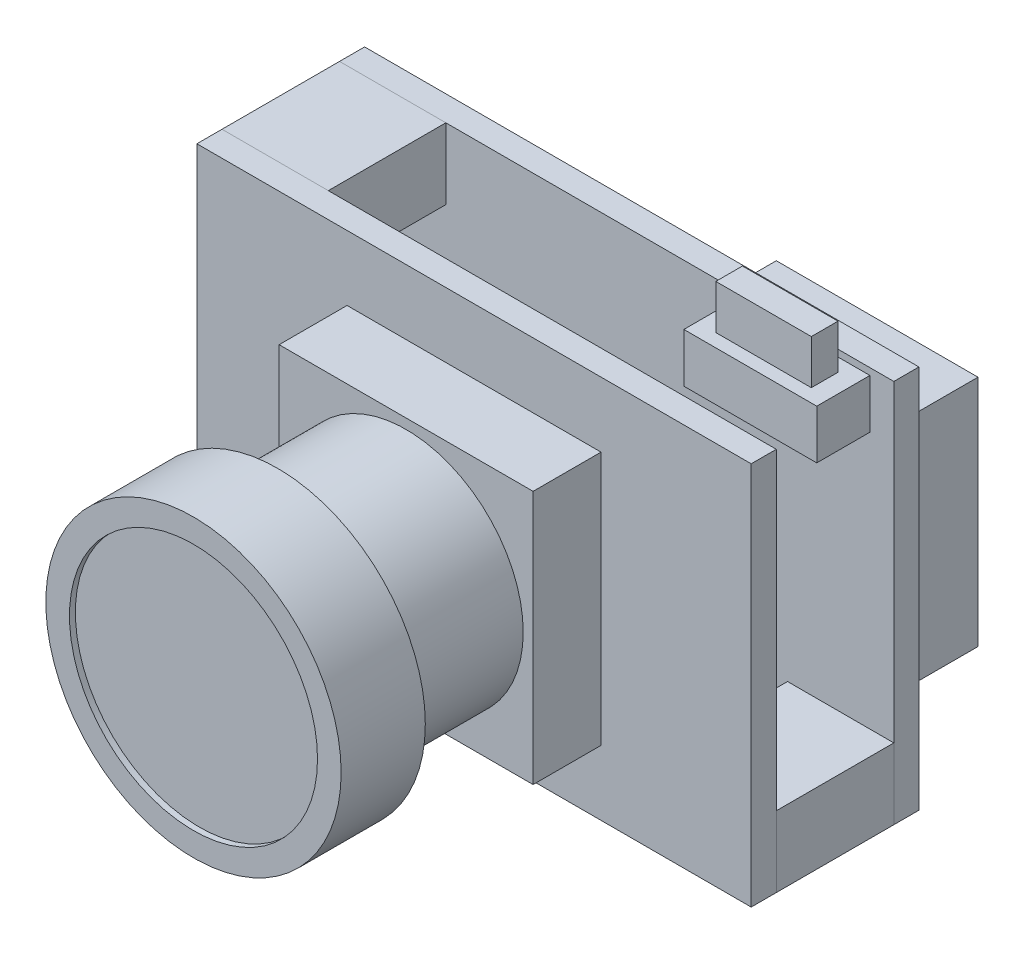
SolidWorks part; units mm, degrees
ref_plane "Front Plane" through (0, 0, 0) normal (0, 0, 1) x (1, 0, 0)
ref_plane "Top Plane" through (0, 0, 0) normal (0, 1, 0) x (1, 0, 0)
ref_plane "Right Plane" through (0, 0, 0) normal (1, 0, 0) x (0, 0, -1)
sketch "Sketch1" plane through (0, 0, 0) normal (0, 0, 1) x (1, 0, 0)
  line L1 (-9.385, 6.5) -> (9.385, 6.5)
  line L2 (-9.385, 6.5) -> (-9.385, -6.5)
  line L3 (-9.385, -6.5) -> (9.385, -6.5)
  line L4 (9.385, 6.5) -> (9.385, -6.5)
  line L5 (-9.385, 6.5) -> (9.385, -6.5) construction
  line L6 (-9.385, -6.5) -> (9.385, 6.5) construction
  point P0 (0, 0)
  dimension "D1" = 13
  dimension "D2" = 18.77
extrude "Boss-Extrude1" add sketch "Sketch1" along normal blind 0.85
sketch "Sketch2" plane through (0, 0, 0.85) normal (0, 0, 1) x (1, 0, 0)
  line L1 (9.385, -6.5) -> (5.785, -6.5)
  line L2 (9.385, -6.5) -> (9.385, -4.1)
  line L3 (9.385, -4.1) -> (5.785, -4.1)
  line L4 (5.785, -6.5) -> (5.785, -4.1)
  line L5 (-9.385, 6.5) -> (-5.785, 6.5)
  line L6 (-9.385, 6.5) -> (-9.385, 4.1)
  line L7 (-9.385, 4.1) -> (-5.785, 4.1)
  line L8 (-5.785, 6.5) -> (-5.785, 4.1)
  dimension "D1" = 2.4
  dimension "D2" = 3.6
extrude "Boss-Extrude2" add sketch "Sketch2" along normal blind 3.98 separate body
sketch "Sketch3" plane through (0, 0, 4.83) normal (0, 0, 1) x (1, 0, 0)
  line L0 (9.385, -6.5) -> (9.385, -4.1) construction
  line L1 (-9.385, 6.5) -> (9.385, 6.5)
  line L2 (-9.385, 6.5) -> (-9.385, -6.5)
  line L3 (-9.385, -6.5) -> (9.385, -6.5)
  line L4 (9.385, 6.5) -> (9.385, -6.5)
  line L5 (5.785, -6.5) -> (9.385, -6.5) construction
extrude "Boss-Extrude3" add sketch "Sketch3" along normal blind 0.85
sketch "Sketch4" plane through (0, 0, 5.68) normal (0, 0, 1) x (1, 0, 0)
  line L1 (-4.3, 4.3) -> (4.3, 4.3)
  line L2 (-4.3, 4.3) -> (-4.3, -4.3)
  line L3 (-4.3, -4.3) -> (4.3, -4.3)
  line L4 (4.3, 4.3) -> (4.3, -4.3)
  line L5 (-4.3, 4.3) -> (4.3, -4.3) construction
  line L6 (-4.3, -4.3) -> (4.3, 4.3) construction
  point P0 (0, 0)
  dimension "D1" = 8.6
extrude "Boss-Extrude4" add sketch "Sketch4" along normal blind 2.3
sketch "Sketch5" plane through (0, 0, 7.98) normal (0, 0, 1) x (1, 0, 0)
  circle A0 centre (0, 0) radius 3.965
  dimension "D1" = 7.93
extrude "Boss-Extrude5" add sketch "Sketch5" along normal blind 4.35
sketch "Sketch6" plane through (0, 0, 12.33) normal (0, 0, 1) x (1, 0, 0)
  circle A0 centre (0, 0) radius 5
  dimension "D1" = 10
extrude "Boss-Extrude6" add sketch "Sketch6" along normal blind 2.85
sketch "Sketch7" plane through (0, 0, 15.18) normal (0, 0, 1) x (1, 0, 0)
  circle A0 centre (0, 0) radius 4.2
  circle A1 centre (0, 0) radius 5 construction
  dimension "D1" = 0.8
extrude "Cut-Extrude1" cut sketch "Sketch7" against normal blind 0.2
sketch "Sketch8" plane through (0, 0, 0) normal (0, 0, -1) x (-1, 0, 0)
  line L0 (-9.385, -6.5) -> (-9.385, 6.5) construction
  line L1 (-9.085, 4.9) -> (-2.255, 4.9)
  line L2 (-9.085, 4.9) -> (-9.085, -3)
  line L3 (-9.085, -3) -> (-2.255, -3)
  line L4 (-2.255, 4.9) -> (-2.255, -3)
  line L5 (-9.385, 6.5) -> (9.385, 6.5) construction
  dimension "D1" = 7.9
  dimension "D2" = 6.83
  dimension "D3" = 0.3
  dimension "D4" = 1.6
extrude "Boss-Extrude7" add sketch "Sketch8" along normal blind 2.3
sketch "Sketch9" plane through (0, 0, 0) normal (0, 0, -1) x (-1, 0, 0)
  line L1 (-0.6481, -5.1764) -> (5.3519, -5.1764)
  line L2 (-0.6481, -5.1764) -> (-0.6481, 0.8236)
  line L3 (-0.6481, 0.8236) -> (5.3519, 0.8236)
  line L4 (5.3519, -5.1764) -> (5.3519, 0.8236)
  dimension "D1" = 6
extrude "Boss-Extrude8" add sketch "Sketch9" along normal blind 1
sketch "Sketch10" plane through (0, 0, 0.85) normal (0, 0, 1) x (1, 0, 0)
  line L1 (8.5749, 6.2701) -> (4.0749, 6.2701)
  line L2 (8.5749, 6.2701) -> (8.5749, 4.6059)
  line L3 (8.5749, 4.6059) -> (4.0749, 4.6059)
  line L4 (4.0749, 6.2701) -> (4.0749, 4.6059)
  dimension "D1" = 4.5
extrude "Boss-Extrude9" add sketch "Sketch10" along normal blind 1.8
sketch "Sketch11" plane through (0, 6.2701, 0) normal (0, 1, 0) x (1, 0, 0)
  line L0 (8.5749, -0.85) -> (4.0749, -2.65) construction
  line L1 (8.5749, -2.65) -> (4.0749, -2.65) construction
  line L2 (4.0749, -2.65) -> (4.0749, -0.85) construction
  line L4 (4.7074, -1.2989) -> (7.9423, -1.2989)
  line L5 (4.7074, -1.2989) -> (4.7074, -2.2011)
  line L6 (4.7074, -2.2011) -> (7.9423, -2.2011)
  line L7 (7.9423, -1.2989) -> (7.9423, -2.2011)
  line L8 (4.7074, -1.2989) -> (7.9423, -2.2011) construction
  line L9 (4.7074, -2.2011) -> (7.9423, -1.2989) construction
  point P7 (6.3249, -1.75)
extrude "Boss-Extrude10" add sketch "Sketch11" along normal blind 1.5
sketch "Sketch12" plane through (0, 0, 0.85) normal (0, 0, 1) x (1, 0, 0)
  line L1 (-3.6639, 1.1451) -> (-6.0818, 1.1451)
  line L2 (-3.6639, 1.1451) -> (-3.6639, -1.1451)
  line L3 (-3.6639, -1.1451) -> (-6.0818, -1.1451)
  line L4 (-6.0818, 1.1451) -> (-6.0818, -1.1451)
  line L5 (-3.6639, 1.1451) -> (-6.0818, -1.1451) construction
  line L6 (-3.6639, -1.1451) -> (-6.0818, 1.1451) construction
  point P0 (-4.8729, 0)
extrude "Boss-Extrude11" add sketch "Sketch12" along normal blind 1.5
sketch "Sketch13" plane through (-6.0818, 0, 0) normal (-1, 0, 0) x (0, 0, 1)
  line L0 (1.6, 1.1451) -> (1.6, -1.1451) construction
  line L1 (2.35, 1.1451) -> (0.85, 1.1451) construction
  line L2 (2.35, -1.1451) -> (0.85, -1.1451) construction
  line L3 (2.35, 0) -> (0.85, 0) construction
  line L4 (2.35, 1.1451) -> (2.35, -1.1451) construction
  line L5 (0.85, 1.1451) -> (0.85, -1.1451) construction
  circle A0 centre (1.6, 0.55) radius 0.45
  circle A1 centre (1.6, -0.55) radius 0.45
  dimension "D1" = 0.9
  dimension "D2" = 1.1
extrude "Boss-Extrude13" add sketch "Sketch13" along normal blind 4
